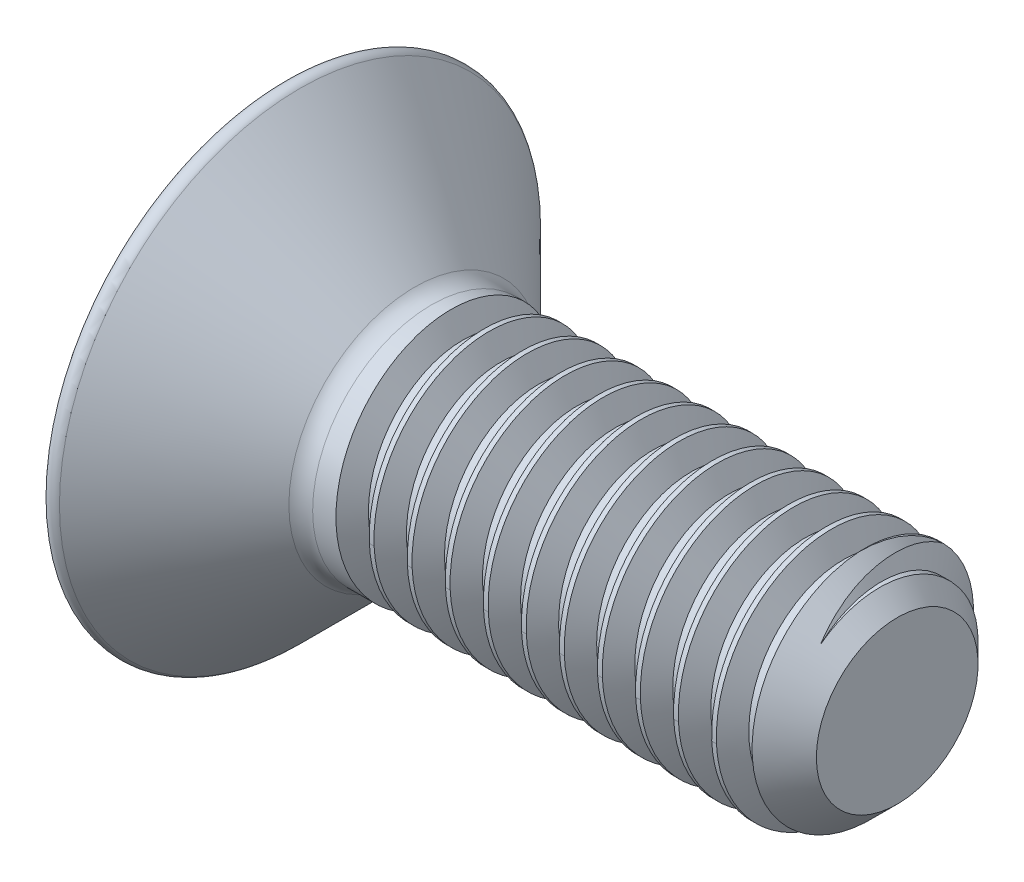
SolidWorks part; units mm, degrees
ref_plane "Front Plane" through (0, 0, 0) normal (0, 0, 1) x (1, 0, 0)
ref_plane "Top Plane" through (0, 0, 0) normal (0, 1, 0) x (1, 0, 0)
ref_plane "Right Plane" through (0, 0, 0) normal (1, 0, 0) x (0, 0, -1)
sketch "Sketch1" plane through (0, 0, 0) normal (0, 0, 1) x (1, 0, 0)
  line L0 (0, 0) -> (23.8703, 0) construction
  line L1 (0, 0) -> (0, 5.4)
  line L2 (0, 5.4) -> (2.7536, 2.6464)
  line L3 (2.9, -2.6119) -> (2.9, 8.9739) construction
  line L4 (3.1071, 2.5) -> (12.9, 2.5)
  line L5 (12.9, 2.5) -> (12.9, 0)
  line L6 (0, 0) -> (12.9, 0)
  arc A0 (2.7536, 2.6464) -> (3.1071, 2.5) centre (3.1071, 3) ccw
  point P8 (23.8703, 0)
  point P13 (2.9, 2.5)
  dimension "D6" = 0.5
  dimension "D1" = 45
  dimension "D2" = 10
  dimension "D3" = 2.9
  dimension "D4" = 2.5
  dimension "D5" = 5.4
revolve "Revolve1" add sketch "Sketch1" angle 360 about L6
chamfer "Chamfer1" distance 0.8 angle 45 1 edges at (12.9, 0, 2.5)
thread "Thread2" pitch 0.8 start angle 0, offset 1, length 0, pitch 0.8, diameter 5
ref_plane "Plane3" through (13.1, 0, 2.5) normal (0, -1, 0) x (0, 0, 1)
sketch "Thread Profile3" plane through (13.1, 0, 2.5) normal (0, -1, 0) x (0, 0, 1)
  line L0 (0, 0) -> (0, 0.8) construction
  line L11 (0, 0) -> (0, 0.7)
  line L12 (0, 0.7) -> (-0.433, 0.45)
  line L13 (-0.433, 0.45) -> (-0.433, 0.25)
  line L15 (-0.433, 0.25) -> (0, 0)
  line L17 (-0.433, 0.35) -> (0, 0.35) construction
  point P2 (0, 0)
  dimension "Pitch" = 0.8
  dimension "Profile_Angle" = 60
  dimension "Profile_Land" = 0.2
  dimension "Profile_Height" = 0.433
sketch "Sketch10" plane through (0, 0.0001, 0) normal (0, 0.9438, -0.3305) x (1, 0, 0)
  line L8 (3.6073, 2.067) -> (3.8573, 2.5)
  line L9 (3.8573, 2.5) -> (3.1573, 2.5)
  line L10 (3.1573, 2.5) -> (3.4073, 2.067)
  line L11 (3.4073, 2.067) -> (3.6073, 2.067)
extrude "Cut-Extrude1" cut sketch "Sketch10" against normal mid plane 10
fillet "Fillet1" radius 0.2 1 edges at (0, 0, 5.4)
sketch "Sketch11" plane through (0, 0, 0) normal (-1, 0, 0) x (0, 0, 1)
  line L1 (0, 1.7436) -> (-1.51, 0.8718)
  line L2 (-1.51, 0.8718) -> (-1.51, -0.8718)
  line L3 (-1.51, -0.8718) -> (0, -1.7436)
  line L4 (0, -1.7436) -> (1.51, -0.8718)
  line L5 (1.51, -0.8718) -> (1.51, 0.8718)
  line L6 (1.51, 0.8718) -> (0, 1.7436)
  circle A0 centre (0, 0) radius 1.51 construction
  dimension "D1" = 3.02
extrude "Cut-Extrude2" cut sketch "Sketch11" against normal blind 2.05 draft 2 contours L6 L1 L2 L3 L4 L5
fillet "Fillet2" radius 0.1 6 edges at (0, 1.3077, -0.755) (0, 0, -1.51) (0, -1.3077, -0.755) (0, -1.3077, 0.755) (0, 0, 1.51) (0, 1.3077, 0.755)
